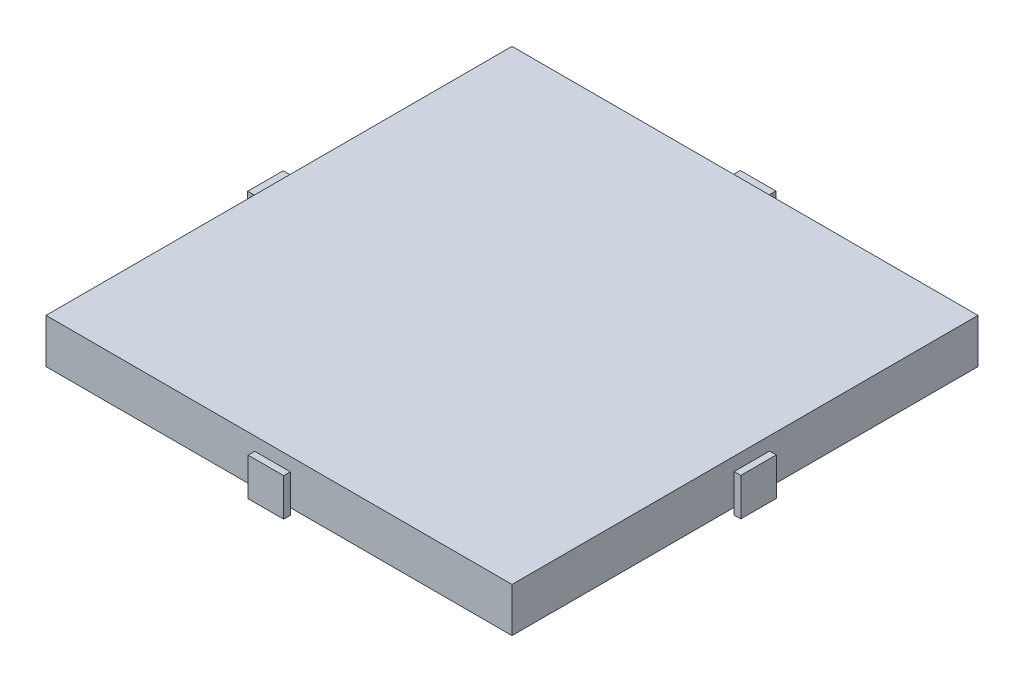
SolidWorks part; units mm, degrees
ref_plane "Front Plane" through (0, 0, 0) normal (0, 0, 1) x (1, 0, 0)
ref_plane "Top Plane" through (0, 0, 0) normal (0, 1, 0) x (1, 0, 0)
ref_plane "Right Plane" through (0, 0, 0) normal (1, 0, 0) x (0, 0, -1)
sketch "CenterSketch1" plane through (0, 0, 0) normal (0, 1, 0) x (1, 0, 0)
  line L1 (0, 0) -> (210, 0)
  line L2 (0, 0) -> (0, 210)
  line L3 (0, 210) -> (210, 210)
  line L4 (210, 0) -> (210, 210)
  dimension "D1" = 210
  dimension "D2" = 210
extrude "CenterBoss-Extrude1" add sketch "CenterSketch1" along normal blind 20
shell "Shell2" thickness 3 removed face at (105, 0, -105)
sketch "CenterPegSketch1" plane through (0, 0, -210) normal (0, 0, -1) x (-1, 0, 0)
  line L0 (-210, 0) -> (0, 0) construction
  line L1 (-109.9, 13.9) -> (-100.1, 13.9)
  line L2 (-109.9, 13.9) -> (-109.9, 0)
  line L3 (-109.9, 0) -> (-100.1, 0)
  line L4 (-100.1, 13.9) -> (-100.1, 0)
  line L6 (-210, 20) -> (-210, 0) construction
  dimension "D1" = 9.8
  dimension "D2" = 13.9
  dimension "D3" = 100.1
extrude "CenterPegBoss-Extrude1" add sketch "CenterPegSketch1" along normal blind 3
sketch "CenterPegCapSketch2" plane through (0, 0, -213) normal (0, 0, -1) x (-1, 0, 0)
  line L0 (-100.1, 0) -> (0, 0) construction
  line L1 (-112.9, 17) -> (-96.9, 17)
  line L2 (-112.9, 17) -> (-112.9, 0)
  line L3 (-112.9, 0) -> (-96.9, 0)
  line L4 (-96.9, 17) -> (-96.9, 0)
  line L5 (-109.9, 13.9) -> (-109.9, 0) construction
  dimension "D1" = 17
  dimension "D2" = 16
  dimension "D3" = 3
extrude "CenterPegCapBoss-Extrude2" add sketch "CenterPegCapSketch2" along normal blind 3
sketch "CenterPegBossSketch3" plane through (210, 0, 0) normal (1, 0, 0) x (0, 0, -1)
  line L0 (0, 0) -> (210, 0) construction
  line L1 (100.1, 13.9) -> (109.9, 13.9)
  line L2 (100.1, 13.9) -> (100.1, 0)
  line L3 (100.1, 0) -> (109.9, 0)
  line L4 (109.9, 13.9) -> (109.9, 0)
  line L5 (0, 20) -> (0, 0) construction
  dimension "D3" = 100.1
  dimension "D1" = 13.9
  dimension "D2" = 9.8
extrude "CenterPegBoss-Extrude3" add sketch "CenterPegBossSketch3" along normal blind 3
sketch "CenterPegCapSketch4" plane through (213, 0, 0) normal (1, 0, 0) x (0, 0, -1)
  line L0 (109.9, 0) -> (210, 0) construction
  line L1 (97.1, 17) -> (113.1, 17)
  line L2 (97.1, 17) -> (97.1, 0)
  line L3 (97.1, 0) -> (113.1, 0)
  line L4 (113.1, 17) -> (113.1, 0)
  line L5 (0, 0) -> (100.1, 0) construction
  line L6 (100.1, 13.9) -> (100.1, 0) construction
  dimension "D1" = 17
  dimension "D2" = 16
  dimension "D3" = 3
sketch "CenterPegSketch5" plane through (0, 0, 0) normal (0, 0, 1) x (1, 0, 0)
  line L0 (0, 0) -> (210, 0) construction
  line L1 (100.1, 13.9) -> (109.9, 13.9)
  line L2 (100.1, 13.9) -> (100.1, 0)
  line L3 (100.1, 0) -> (109.9, 0)
  line L4 (109.9, 13.9) -> (109.9, 0)
  line L5 (0, 20) -> (0, 0) construction
  dimension "D3" = 100.1
  dimension "D1" = 13.9
  dimension "D2" = 9.8
extrude "CenterPegCapBoss-Extrude4" add sketch "CenterPegCapSketch4" along normal blind 3
extrude "CenterPegBoss-Extrude5" add sketch "CenterPegSketch5" along normal blind 3
sketch "CenterPegCapSketch6" plane through (0, 0, 3) normal (0, 0, 1) x (1, 0, 0)
  line L0 (109.9, 0) -> (210, 0) construction
  line L1 (97.1, 17) -> (113.1, 17)
  line L2 (97.1, 17) -> (97.1, 0)
  line L3 (97.1, 0) -> (113.1, 0)
  line L4 (113.1, 17) -> (113.1, 0)
  line L5 (0, 0) -> (100.1, 0) construction
  line L6 (100.1, 13.9) -> (100.1, 0) construction
  dimension "D1" = 17
  dimension "D2" = 16
  dimension "D3" = 3
extrude "CenterPegCapBoss-Extrude6" add sketch "CenterPegCapSketch6" along normal blind 3
sketch "CenterPegSketch7" plane through (0, 0, 0) normal (-1, 0, 0) x (0, 0, 1)
  line L0 (-210, 0) -> (0, 0) construction
  line L1 (-109.9, 13.9) -> (-100.1, 13.9)
  line L2 (-109.9, 13.9) -> (-109.9, 0)
  line L3 (-109.9, 0) -> (-100.1, 0)
  line L4 (-100.1, 13.9) -> (-100.1, 0)
  line L5 (-210, 20) -> (-210, 0) construction
  dimension "D3" = 100.1
  dimension "D1" = 13.9
  dimension "D2" = 9.8
extrude "CenterPegBoss-Extrude7" add sketch "CenterPegSketch7" along normal blind 3
sketch "CenterPegCapSketch8" plane through (-3, 0, 0) normal (-1, 0, 0) x (0, 0, 1)
  line L0 (-100.1, 0) -> (0, 0) construction
  line L1 (-112.9, 17) -> (-96.9, 17)
  line L2 (-112.9, 17) -> (-112.9, 0)
  line L3 (-112.9, 0) -> (-96.9, 0)
  line L4 (-96.9, 17) -> (-96.9, 0)
  line L5 (-210, 0) -> (-109.9, 0) construction
  line L7 (-109.9, 13.9) -> (-109.9, 0) construction
  dimension "D1" = 17
  dimension "D2" = 16
  dimension "D3" = 3
extrude "CenterPegCapBoss-Extrude8" add sketch "CenterPegCapSketch8" along normal blind 3
equation "\"BedThickness\"= 20mm"
equation "\"BedThirdSize\"= 70mm"
equation "\"D1@CenterBoss-Extrude1\"=\"BedThickness\""
equation "\"BedInnerSquareWidth\"= \"BedThirdSize\" * 3'Equals 210"
equation "\"BedInnerSquareLength\"= \"BedInnerSquareWidth\""
equation "\"D1@CenterSketch1\"=\"BedInnerSquareLength\""
equation "\"D2@CenterSketch1\"=\"BedInnerSquareWidth\""
equation "\"D1\"= \"BedThickness\""
equation "\"D3\"= \"BedOverlap\""
equation "\"StandardWallThickness\"= 3mm"
equation "\"BedPegHoleWidth\"= 10mm"
equation "\"BedPegHoleHeight\"= \"BedThickness\" - \"StandardWallThickness\" * 2'Equals 14"
equation "\"BedPegWidth\"= \"BedPegHoleWidth\" - .1mm * 2'For easier assembly"
equation "\"BedPegHeight\"= \"BedPegHoleHeight\" - .1mm'For easier assembly"
equation "\"BedPegCapHeight\"= \"BedThickness\" - \"StandardWallThickness\"'Equals 17"
equation "\"BedPegCapWidth\"= \"BedThickness\" / 2 + \"StandardWallThickness\" * 2'Equals 16"
equation "\"D1@CenterPegSketch1\" = \"BedPegWidth\""
equation "\"D2@CenterPegSketch1\" = \"BedPegHeight\""
equation "\"D3@CenterPegSketch1\" = \"BedInnerSquareWidth\" / 2 - \"BedPegWidth\" / 2"
equation "\"D1@CenterPegCapSketch2\" = \"BedPegCapHeight\""
equation "\"D2@CenterPegCapSketch2\" = \"BedPegCapWidth\""
equation "\"D3@CenterPegCapSketch2\" = \"StandardWallThickness\""
equation "\"D1@CenterPegCapBoss-Extrude2\" = \"StandardWallThickness\""
equation "\"D1@CenterPegBossSketch3\" = \"BedPegHeight\""
equation "\"D2@CenterPegBossSketch3\" = \"BedPegWidth\""
equation "\"D3@CenterPegBossSketch3\" = \"BedInnerSquareLength\" / 2 - \"BedPegWidth\" / 2"
equation "\"D1@CenterPegBoss-Extrude3\"=\"StandardWallThickness\""
equation "\"D1@CenterPegCapSketch4\" = \"BedPegCapHeight\""
equation "\"D2@CenterPegCapSketch4\" = \"BedPegCapWidth\""
equation "\"D3@CenterPegCapSketch4\" = \"StandardWallThickness\""
equation "\"D1@CenterPegSketch5\" = \"BedPegHeight\""
equation "\"D2@CenterPegSketch5\" = \"BedPegWidth\""
equation "\"D3@CenterPegSketch5\" = \"BedInnerSquareWidth\" / 2 - \"BedPegWidth\" / 2"
equation "\"D1@CenterPegCapBoss-Extrude4\" = \"StandardWallThickness\""
equation "\"D1@CenterPegBoss-Extrude5\"=\"StandardWallThickness\""
equation "\"D1@CenterPegCapSketch6\" = \"BedPegCapHeight\""
equation "\"D2@CenterPegCapSketch6\" = \"BedPegCapWidth\""
equation "\"D3@CenterPegCapSketch6\" = \"StandardWallThickness\""
equation "\"D1@CenterPegCapBoss-Extrude6\" = \"StandardWallThickness\""
equation "\"D1@CenterPegSketch7\" = \"BedPegHeight\""
equation "\"D2@CenterPegSketch7\" = \"BedPegWidth\""
equation "\"D3@CenterPegSketch7\"=\"BedInnerSquareLength\" / 2 - \"BedPegWidth\" / 2"
equation "\"D1@CenterPegBoss-Extrude7\" = \"StandardWallThickness\""
equation "\"D1@CenterPegCapSketch8\" = \"BedPegCapHeight\""
equation "\"D2@CenterPegCapSketch8\" = \"BedPegCapWidth\""
equation "\"D3@CenterPegCapSketch8\" = \"StandardWallThickness\""
equation "\"D1@CenterPegCapBoss-Extrude8\"=\"StandardWallThickness\""
